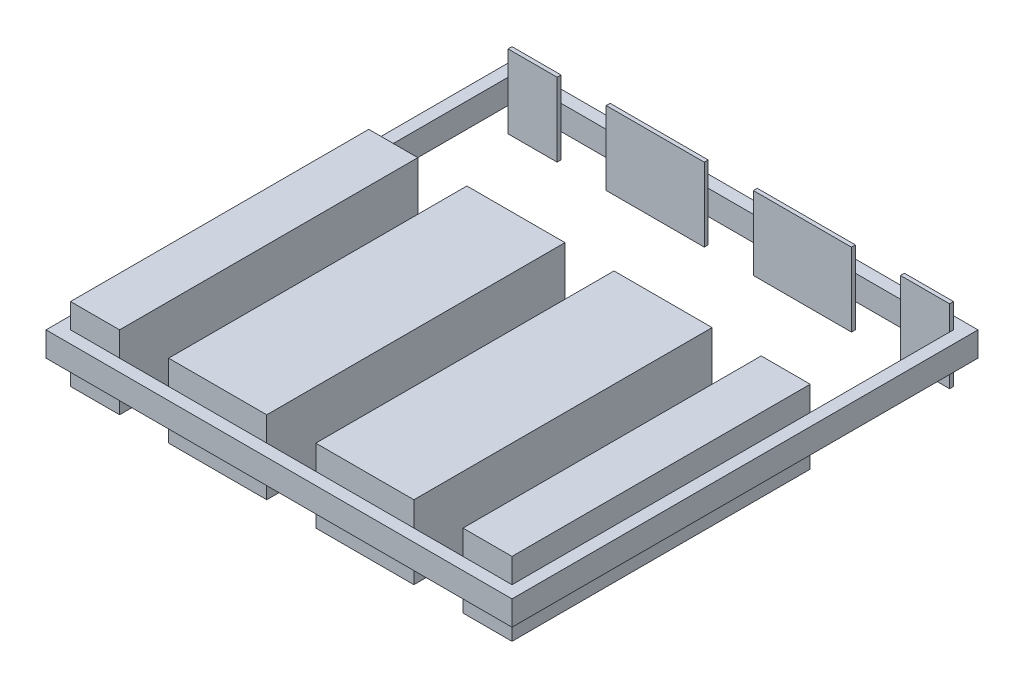
SolidWorks part; units mm, degrees
material "ABS"
ref_plane "Front Plane" through (0, 0, 0) normal (0, 0, 1) x (1, 0, 0)
ref_plane "Top Plane" through (0, 0, 0) normal (0, 1, 0) x (1, 0, 0)
ref_plane "Right Plane" through (0, 0, 0) normal (1, 0, 0) x (0, 0, -1)
sketch "Sketch1" plane through (0, 0, 0) normal (0, 0, 1) x (1, 0, 0)
  line L1 (-90, -15) -> (90, -15)
  line L2 (-90, -15) -> (-90, 15)
  line L3 (-90, 15) -> (90, 15)
  line L4 (90, -15) -> (90, 15)
  line L5 (0, 15) -> (0, -15) construction
  line L6 (-90, 0) -> (90, 0) construction
  point P16 (0, 0)
extrude "Boss-Extrude1" add sketch "Sketch1" along normal mid plane 180
sketch "Sketch2" plane through (0, 0, 0) normal (0, 0, 1) x (1, 0, 0)
  line L0 (-90, -15) -> (90, -15) construction
  line L1 (-70, -15) -> (-50, -15)
  line L2 (-70, -15) -> (-70, 15)
  line L3 (-70, 15) -> (-50, 15)
  line L4 (-50, -15) -> (-50, 15)
  line L5 (-60, 15) -> (-60, -15) construction
  line L6 (-70, 0) -> (-50, 0) construction
  line L7 (90, 15) -> (-90, 15) construction
  line L9 (-10, -15) -> (10, -15)
  line L10 (-10, -15) -> (-10, 15)
  line L11 (-10, 15) -> (10, 15)
  line L12 (10, -15) -> (10, 15)
  line L13 (0, 15) -> (0, -15) construction
  line L14 (-10, 0) -> (10, 0) construction
  line L15 (50, -15) -> (70, -15)
  line L16 (50, -15) -> (50, 15)
  line L17 (50, 15) -> (70, 15)
  line L18 (70, -15) -> (70, 15)
  line L19 (60, 15) -> (60, -15) construction
  line L20 (50, 0) -> (70, 0) construction
  point P20 (-60, 0)
  point P33 (0, 0)
  point P42 (60, 0)
extrude "Cut-Extrude1" cut sketch "Sketch2" against normal mid plane 180
sketch "Sketch3" plane through (0, 0, 0) normal (0, 0, 1) x (1, 0, 0)
  line L1 (-88.4, -13.4) -> (-71.6, -13.4)
  line L2 (-88.4, -13.4) -> (-88.4, 13.4)
  line L3 (-88.4, 13.4) -> (-71.6, 13.4)
  line L4 (-71.6, -13.4) -> (-71.6, 13.4)
  line L5 (-80, 13.4) -> (-80, -13.4) construction
  line L6 (-88.4, 0) -> (-71.6, 0) construction
  line L7 (-48.4, -13.4) -> (-31.6, -13.4)
  line L8 (-48.4, -13.4) -> (-48.4, 13.4)
  line L9 (-48.4, 13.4) -> (-31.6, 13.4)
  line L10 (-31.6, -13.4) -> (-31.6, 13.4)
  line L11 (-40, 13.4) -> (-40, -13.4) construction
  line L12 (-48.4, 0) -> (-31.6, 0) construction
  line L13 (-28.4, -13.4) -> (-11.6, -13.4)
  line L14 (-28.4, -13.4) -> (-28.4, 13.4)
  line L15 (-28.4, 13.4) -> (-11.6, 13.4)
  line L16 (-11.6, -13.4) -> (-11.6, 13.4)
  line L17 (-20, 13.4) -> (-20, -13.4) construction
  line L18 (-28.4, 0) -> (-11.6, 0) construction
  line L19 (11.6, -13.4) -> (28.4, -13.4)
  line L20 (11.6, -13.4) -> (11.6, 13.4)
  line L21 (11.6, 13.4) -> (28.4, 13.4)
  line L22 (28.4, -13.4) -> (28.4, 13.4)
  line L23 (20, 13.4) -> (20, -13.4) construction
  line L24 (11.6, 0) -> (28.4, 0) construction
  line L25 (31.6, -13.4) -> (48.4, -13.4)
  line L26 (31.6, -13.4) -> (31.6, 13.4)
  line L27 (31.6, 13.4) -> (48.4, 13.4)
  line L28 (48.4, -13.4) -> (48.4, 13.4)
  line L29 (40, 13.4) -> (40, -13.4) construction
  line L30 (31.6, 0) -> (48.4, 0) construction
  line L31 (71.6, -13.4) -> (88.4, -13.4)
  line L32 (71.6, -13.4) -> (71.6, 13.4)
  line L33 (71.6, 13.4) -> (88.4, 13.4)
  line L34 (88.4, -13.4) -> (88.4, 13.4)
  line L35 (80, 13.4) -> (80, -13.4) construction
  line L36 (71.6, 0) -> (88.4, 0) construction
  point P16 (-80, 0)
  point P25 (-40, 0)
  point P34 (-20, 0)
  point P43 (20, 0)
  point P52 (40, 0)
  point P61 (80, 0)
extrude "Cut-Extrude2" cut sketch "Sketch3" against normal blind 56.8 from offset 31.6 flip side to cut offset against normal yes
sketch "Sketch4" plane through (0, 0, 0) normal (0, 0, 1) x (1, 0, 0)
  line L1 (-88.4, -13.4) -> (-71.6, -13.4)
  line L2 (-88.4, -13.4) -> (-88.4, 13.4)
  line L3 (-88.4, 13.4) -> (-71.6, 13.4)
  line L4 (-71.6, -13.4) -> (-71.6, 13.4)
  line L5 (-80, 13.4) -> (-80, -13.4) construction
  line L6 (-88.4, 0) -> (-71.6, 0) construction
  line L7 (-48.4, -13.4) -> (-31.6, -13.4)
  line L8 (-48.4, -13.4) -> (-48.4, 13.4)
  line L9 (-48.4, 13.4) -> (-31.6, 13.4)
  line L10 (-31.6, -13.4) -> (-31.6, 13.4)
  line L11 (-40, 13.4) -> (-40, -13.4) construction
  line L12 (-48.4, 0) -> (-31.6, 0) construction
  line L13 (-28.4, -13.4) -> (-11.6, -13.4)
  line L14 (-28.4, -13.4) -> (-28.4, 13.4)
  line L15 (-28.4, 13.4) -> (-11.6, 13.4)
  line L16 (-11.6, -13.4) -> (-11.6, 13.4)
  line L17 (-20, 13.4) -> (-20, -13.4) construction
  line L18 (-28.4, 0) -> (-11.6, 0) construction
  line L19 (11.6, -13.4) -> (28.4, -13.4)
  line L20 (11.6, -13.4) -> (11.6, 13.4)
  line L21 (11.6, 13.4) -> (28.4, 13.4)
  line L22 (28.4, -13.4) -> (28.4, 13.4)
  line L23 (20, 13.4) -> (20, -13.4) construction
  line L24 (11.6, 0) -> (28.4, 0) construction
  line L25 (31.6, -13.4) -> (48.4, -13.4)
  line L26 (31.6, -13.4) -> (31.6, 13.4)
  line L27 (31.6, 13.4) -> (48.4, 13.4)
  line L28 (48.4, -13.4) -> (48.4, 13.4)
  line L29 (40, 13.4) -> (40, -13.4) construction
  line L30 (31.6, 0) -> (48.4, 0) construction
  line L31 (71.6, -13.4) -> (88.4, -13.4)
  line L32 (71.6, -13.4) -> (71.6, 13.4)
  line L33 (71.6, 13.4) -> (88.4, 13.4)
  line L34 (88.4, -13.4) -> (88.4, 13.4)
  line L35 (80, 13.4) -> (80, -13.4) construction
  line L36 (71.6, 0) -> (88.4, 0) construction
  point P16 (-80, 0)
  point P25 (-40, 0)
  point P34 (-20, 0)
  point P43 (20, 0)
  point P52 (40, 0)
  point P61 (80, 0)
extrude "Cut-Extrude3" cut sketch "Sketch4" against normal mid plane 56.8
sketch "Sketch5" plane through (0, 0, 0) normal (0, 0, 1) x (1, 0, 0)
  line L1 (-88.4, -13.4) -> (-71.6, -13.4)
  line L2 (-88.4, -13.4) -> (-88.4, 13.4)
  line L3 (-88.4, 13.4) -> (-71.6, 13.4)
  line L4 (-71.6, -13.4) -> (-71.6, 13.4)
  line L5 (-80, 13.4) -> (-80, -13.4) construction
  line L6 (-88.4, 0) -> (-71.6, 0) construction
  line L7 (-48.4, -13.4) -> (-31.6, -13.4)
  line L8 (-48.4, -13.4) -> (-48.4, 13.4)
  line L9 (-48.4, 13.4) -> (-31.6, 13.4)
  line L10 (-31.6, -13.4) -> (-31.6, 13.4)
  line L11 (-40, 13.4) -> (-40, -13.4) construction
  line L12 (-48.4, 0) -> (-31.6, 0) construction
  line L13 (-28.4, -13.4) -> (-11.6, -13.4)
  line L14 (-28.4, -13.4) -> (-28.4, 13.4)
  line L15 (-28.4, 13.4) -> (-11.6, 13.4)
  line L16 (-11.6, -13.4) -> (-11.6, 13.4)
  line L17 (-20, 13.4) -> (-20, -13.4) construction
  line L18 (-28.4, 0) -> (-11.6, 0) construction
  line L19 (11.6, -13.4) -> (28.4, -13.4)
  line L20 (11.6, -13.4) -> (11.6, 13.4)
  line L21 (11.6, 13.4) -> (28.4, 13.4)
  line L22 (28.4, -13.4) -> (28.4, 13.4)
  line L23 (20, 13.4) -> (20, -13.4) construction
  line L24 (11.6, 0) -> (28.4, 0) construction
  line L25 (31.6, -13.4) -> (48.4, -13.4)
  line L26 (31.6, -13.4) -> (31.6, 13.4)
  line L27 (31.6, 13.4) -> (48.4, 13.4)
  line L28 (48.4, -13.4) -> (48.4, 13.4)
  line L29 (40, 13.4) -> (40, -13.4) construction
  line L30 (31.6, 0) -> (48.4, 0) construction
  line L31 (71.6, -13.4) -> (88.4, -13.4)
  line L32 (71.6, -13.4) -> (71.6, 13.4)
  line L33 (71.6, 13.4) -> (88.4, 13.4)
  line L34 (88.4, -13.4) -> (88.4, 13.4)
  line L35 (80, 13.4) -> (80, -13.4) construction
  line L36 (71.6, 0) -> (88.4, 0) construction
  point P16 (-80, 0)
  point P25 (-40, 0)
  point P34 (-20, 0)
  point P43 (20, 0)
  point P52 (40, 0)
  point P61 (80, 0)
extrude "Cut-Extrude4" cut sketch "Sketch5" against normal blind 56.8 from offset 31.6
sketch "Sketch6" plane through (0, 0, 0) normal (0, 0, 1) x (1, 0, 0)
  line L1 (-76.2, -13.4) -> (-74.6, -13.4)
  line L2 (-76.2, -13.4) -> (-76.2, 10.4)
  line L3 (-76.2, 10.4) -> (-74.6, 10.4)
  line L4 (-74.6, -13.4) -> (-74.6, 10.4)
  line L5 (-75.4, 10.4) -> (-75.4, -13.4) construction
  line L6 (-76.2, -1.5) -> (-74.6, -1.5) construction
  line L7 (-80.8, -10.4) -> (-79.2, -10.4)
  line L8 (-80.8, -10.4) -> (-80.8, 13.4)
  line L9 (-80.8, 13.4) -> (-79.2, 13.4)
  line L10 (-79.2, -10.4) -> (-79.2, 13.4)
  line L11 (-80, 13.4) -> (-80, -10.4) construction
  line L12 (-80.8, 1.5) -> (-79.2, 1.5) construction
  line L13 (-85.4, -13.4) -> (-83.8, -13.4)
  line L14 (-85.4, -13.4) -> (-85.4, 10.4)
  line L15 (-85.4, 10.4) -> (-83.8, 10.4)
  line L16 (-83.8, -13.4) -> (-83.8, 10.4)
  line L17 (-84.6, 10.4) -> (-84.6, -13.4) construction
  line L18 (-85.4, -1.5) -> (-83.8, -1.5) construction
  line L19 (-45.4, -13.4) -> (-43.8, -13.4)
  line L20 (-45.4, -13.4) -> (-45.4, 10.4)
  line L21 (-45.4, 10.4) -> (-43.8, 10.4)
  line L22 (-43.8, -13.4) -> (-43.8, 10.4)
  line L23 (-44.6, 10.4) -> (-44.6, -13.4) construction
  line L24 (-45.4, -1.5) -> (-43.8, -1.5) construction
  line L25 (-40.8, -10.4) -> (-39.2, -10.4)
  line L26 (-40.8, -10.4) -> (-40.8, 13.4)
  line L27 (-40.8, 13.4) -> (-39.2, 13.4)
  line L28 (-39.2, -10.4) -> (-39.2, 13.4)
  line L29 (-40, 13.4) -> (-40, -10.4) construction
  line L30 (-40.8, 1.5) -> (-39.2, 1.5) construction
  line L31 (-36.2, -13.4) -> (-34.6, -13.4)
  line L32 (-36.2, -13.4) -> (-36.2, 10.4)
  line L33 (-36.2, 10.4) -> (-34.6, 10.4)
  line L34 (-34.6, -13.4) -> (-34.6, 10.4)
  line L35 (-35.4, 10.4) -> (-35.4, -13.4) construction
  line L36 (-36.2, -1.5) -> (-34.6, -1.5) construction
  line L37 (-16.2, -13.4) -> (-14.6, -13.4)
  line L38 (-16.2, -13.4) -> (-16.2, 10.4)
  line L39 (-16.2, 10.4) -> (-14.6, 10.4)
  line L40 (-14.6, -13.4) -> (-14.6, 10.4)
  line L41 (-15.4, 10.4) -> (-15.4, -13.4) construction
  line L42 (-16.2, -1.5) -> (-14.6, -1.5) construction
  line L43 (-20.8, -10.4) -> (-19.2, -10.4)
  line L44 (-20.8, -10.4) -> (-20.8, 13.4)
  line L45 (-20.8, 13.4) -> (-19.2, 13.4)
  line L46 (-19.2, -10.4) -> (-19.2, 13.4)
  line L47 (-20, 13.4) -> (-20, -10.4) construction
  line L48 (-20.8, 1.5) -> (-19.2, 1.5) construction
  line L49 (-25.4, -13.4) -> (-23.8, -13.4)
  line L50 (-25.4, -13.4) -> (-25.4, 10.4)
  line L51 (-25.4, 10.4) -> (-23.8, 10.4)
  line L52 (-23.8, -13.4) -> (-23.8, 10.4)
  line L53 (-24.6, 10.4) -> (-24.6, -13.4) construction
  line L54 (-25.4, -1.5) -> (-23.8, -1.5) construction
  line L55 (14.6, -13.4) -> (16.2, -13.4)
  line L56 (14.6, -13.4) -> (14.6, 10.4)
  line L57 (14.6, 10.4) -> (16.2, 10.4)
  line L58 (16.2, -13.4) -> (16.2, 10.4)
  line L59 (15.4, 10.4) -> (15.4, -13.4) construction
  line L60 (14.6, -1.5) -> (16.2, -1.5) construction
  line L61 (19.2, -10.4) -> (20.8, -10.4)
  line L62 (19.2, -10.4) -> (19.2, 13.4)
  line L63 (19.2, 13.4) -> (20.8, 13.4)
  line L64 (20.8, -10.4) -> (20.8, 13.4)
  line L65 (20, 13.4) -> (20, -10.4) construction
  line L66 (19.2, 1.5) -> (20.8, 1.5) construction
  line L67 (23.8, -13.4) -> (25.4, -13.4)
  line L68 (23.8, -13.4) -> (23.8, 10.4)
  line L69 (23.8, 10.4) -> (25.4, 10.4)
  line L70 (25.4, -13.4) -> (25.4, 10.4)
  line L71 (24.6, 10.4) -> (24.6, -13.4) construction
  line L72 (23.8, -1.5) -> (25.4, -1.5) construction
  line L73 (43.8, -13.4) -> (45.4, -13.4)
  line L74 (43.8, -13.4) -> (43.8, 10.4)
  line L75 (43.8, 10.4) -> (45.4, 10.4)
  line L76 (45.4, -13.4) -> (45.4, 10.4)
  line L77 (44.6, 10.4) -> (44.6, -13.4) construction
  line L78 (43.8, -1.5) -> (45.4, -1.5) construction
  line L79 (39.2, -10.4) -> (40.8, -10.4)
  line L80 (39.2, -10.4) -> (39.2, 13.4)
  line L81 (39.2, 13.4) -> (40.8, 13.4)
  line L82 (40.8, -10.4) -> (40.8, 13.4)
  line L83 (40, 13.4) -> (40, -10.4) construction
  line L84 (39.2, 1.5) -> (40.8, 1.5) construction
  line L85 (34.6, -13.4) -> (36.2, -13.4)
  line L86 (34.6, -13.4) -> (34.6, 10.4)
  line L87 (34.6, 10.4) -> (36.2, 10.4)
  line L88 (36.2, -13.4) -> (36.2, 10.4)
  line L89 (35.4, 10.4) -> (35.4, -13.4) construction
  line L90 (34.6, -1.5) -> (36.2, -1.5) construction
  line L91 (74.6, -13.4) -> (76.2, -13.4)
  line L92 (74.6, -13.4) -> (74.6, 10.4)
  line L93 (74.6, 10.4) -> (76.2, 10.4)
  line L94 (76.2, -13.4) -> (76.2, 10.4)
  line L95 (75.4, 10.4) -> (75.4, -13.4) construction
  line L96 (74.6, -1.5) -> (76.2, -1.5) construction
  line L97 (79.2, -10.4) -> (80.8, -10.4)
  line L98 (79.2, -10.4) -> (79.2, 13.4)
  line L99 (79.2, 13.4) -> (80.8, 13.4)
  line L100 (80.8, -10.4) -> (80.8, 13.4)
  line L101 (80, 13.4) -> (80, -10.4) construction
  line L102 (79.2, 1.5) -> (80.8, 1.5) construction
  line L103 (83.8, -13.4) -> (85.4, -13.4)
  line L104 (83.8, -13.4) -> (83.8, 10.4)
  line L105 (83.8, 10.4) -> (85.4, 10.4)
  line L106 (85.4, -13.4) -> (85.4, 10.4)
  line L107 (84.6, 10.4) -> (84.6, -13.4) construction
  line L108 (83.8, -1.5) -> (85.4, -1.5) construction
  point P16 (-75.4, -1.5)
  point P25 (-80, 1.5)
  point P34 (-84.6, -1.5)
  point P43 (-44.6, -1.5)
  point P52 (-40, 1.5)
  point P61 (-35.4, -1.5)
  point P70 (-15.4, -1.5)
  point P79 (-20, 1.5)
  point P88 (-24.6, -1.5)
  point P97 (15.4, -1.5)
  point P106 (20, 1.5)
  point P115 (24.6, -1.5)
  point P124 (44.6, -1.5)
  point P133 (40, 1.5)
  point P142 (35.4, -1.5)
  point P151 (75.4, -1.5)
  point P160 (80, 1.5)
  point P169 (84.6, -1.5)
extrude "Boss-Extrude2" add sketch "Sketch6" along normal blind 56.8 from offset 31.6 flip side to cut offset against normal yes
sketch "Sketch7" plane through (0, 0, 0) normal (0, 0, 1) x (1, 0, 0)
  line L1 (-76.2, -13.4) -> (-74.6, -13.4)
  line L2 (-76.2, -13.4) -> (-76.2, 10.4)
  line L3 (-76.2, 10.4) -> (-74.6, 10.4)
  line L4 (-74.6, -13.4) -> (-74.6, 10.4)
  line L5 (-75.4, 10.4) -> (-75.4, -13.4) construction
  line L6 (-76.2, -1.5) -> (-74.6, -1.5) construction
  line L7 (-80.8, -10.4) -> (-79.2, -10.4)
  line L8 (-80.8, -10.4) -> (-80.8, 13.4)
  line L9 (-80.8, 13.4) -> (-79.2, 13.4)
  line L10 (-79.2, -10.4) -> (-79.2, 13.4)
  line L11 (-80, 13.4) -> (-80, -10.4) construction
  line L12 (-80.8, 1.5) -> (-79.2, 1.5) construction
  line L13 (-85.4, -13.4) -> (-83.8, -13.4)
  line L14 (-85.4, -13.4) -> (-85.4, 10.4)
  line L15 (-85.4, 10.4) -> (-83.8, 10.4)
  line L16 (-83.8, -13.4) -> (-83.8, 10.4)
  line L17 (-84.6, 10.4) -> (-84.6, -13.4) construction
  line L18 (-85.4, -1.5) -> (-83.8, -1.5) construction
  line L19 (-45.4, -13.4) -> (-43.8, -13.4)
  line L20 (-45.4, -13.4) -> (-45.4, 10.4)
  line L21 (-45.4, 10.4) -> (-43.8, 10.4)
  line L22 (-43.8, -13.4) -> (-43.8, 10.4)
  line L23 (-44.6, 10.4) -> (-44.6, -13.4) construction
  line L24 (-45.4, -1.5) -> (-43.8, -1.5) construction
  line L25 (-40.8, -10.4) -> (-39.2, -10.4)
  line L26 (-40.8, -10.4) -> (-40.8, 13.4)
  line L27 (-40.8, 13.4) -> (-39.2, 13.4)
  line L28 (-39.2, -10.4) -> (-39.2, 13.4)
  line L29 (-40, 13.4) -> (-40, -10.4) construction
  line L30 (-40.8, 1.5) -> (-39.2, 1.5) construction
  line L31 (-36.2, -13.4) -> (-34.6, -13.4)
  line L32 (-36.2, -13.4) -> (-36.2, 10.4)
  line L33 (-36.2, 10.4) -> (-34.6, 10.4)
  line L34 (-34.6, -13.4) -> (-34.6, 10.4)
  line L35 (-35.4, 10.4) -> (-35.4, -13.4) construction
  line L36 (-36.2, -1.5) -> (-34.6, -1.5) construction
  line L37 (-16.2, -13.4) -> (-14.6, -13.4)
  line L38 (-16.2, -13.4) -> (-16.2, 10.4)
  line L39 (-16.2, 10.4) -> (-14.6, 10.4)
  line L40 (-14.6, -13.4) -> (-14.6, 10.4)
  line L41 (-15.4, 10.4) -> (-15.4, -13.4) construction
  line L42 (-16.2, -1.5) -> (-14.6, -1.5) construction
  line L43 (-20.8, -10.4) -> (-19.2, -10.4)
  line L44 (-20.8, -10.4) -> (-20.8, 13.4)
  line L45 (-20.8, 13.4) -> (-19.2, 13.4)
  line L46 (-19.2, -10.4) -> (-19.2, 13.4)
  line L47 (-20, 13.4) -> (-20, -10.4) construction
  line L48 (-20.8, 1.5) -> (-19.2, 1.5) construction
  line L49 (-25.4, -13.4) -> (-23.8, -13.4)
  line L50 (-25.4, -13.4) -> (-25.4, 10.4)
  line L51 (-25.4, 10.4) -> (-23.8, 10.4)
  line L52 (-23.8, -13.4) -> (-23.8, 10.4)
  line L53 (-24.6, 10.4) -> (-24.6, -13.4) construction
  line L54 (-25.4, -1.5) -> (-23.8, -1.5) construction
  line L55 (14.6, -13.4) -> (16.2, -13.4)
  line L56 (14.6, -13.4) -> (14.6, 10.4)
  line L57 (14.6, 10.4) -> (16.2, 10.4)
  line L58 (16.2, -13.4) -> (16.2, 10.4)
  line L59 (15.4, 10.4) -> (15.4, -13.4) construction
  line L60 (14.6, -1.5) -> (16.2, -1.5) construction
  line L61 (19.2, -10.4) -> (20.8, -10.4)
  line L62 (19.2, -10.4) -> (19.2, 13.4)
  line L63 (19.2, 13.4) -> (20.8, 13.4)
  line L64 (20.8, -10.4) -> (20.8, 13.4)
  line L65 (20, 13.4) -> (20, -10.4) construction
  line L66 (19.2, 1.5) -> (20.8, 1.5) construction
  line L67 (23.8, -13.4) -> (25.4, -13.4)
  line L68 (23.8, -13.4) -> (23.8, 10.4)
  line L69 (23.8, 10.4) -> (25.4, 10.4)
  line L70 (25.4, -13.4) -> (25.4, 10.4)
  line L71 (24.6, 10.4) -> (24.6, -13.4) construction
  line L72 (23.8, -1.5) -> (25.4, -1.5) construction
  line L73 (43.8, -13.4) -> (45.4, -13.4)
  line L74 (43.8, -13.4) -> (43.8, 10.4)
  line L75 (43.8, 10.4) -> (45.4, 10.4)
  line L76 (45.4, -13.4) -> (45.4, 10.4)
  line L77 (44.6, 10.4) -> (44.6, -13.4) construction
  line L78 (43.8, -1.5) -> (45.4, -1.5) construction
  line L79 (39.2, -10.4) -> (40.8, -10.4)
  line L80 (39.2, -10.4) -> (39.2, 13.4)
  line L81 (39.2, 13.4) -> (40.8, 13.4)
  line L82 (40.8, -10.4) -> (40.8, 13.4)
  line L83 (40, 13.4) -> (40, -10.4) construction
  line L84 (39.2, 1.5) -> (40.8, 1.5) construction
  line L85 (34.6, -13.4) -> (36.2, -13.4)
  line L86 (34.6, -13.4) -> (34.6, 10.4)
  line L87 (34.6, 10.4) -> (36.2, 10.4)
  line L88 (36.2, -13.4) -> (36.2, 10.4)
  line L89 (35.4, 10.4) -> (35.4, -13.4) construction
  line L90 (34.6, -1.5) -> (36.2, -1.5) construction
  line L91 (74.6, -13.4) -> (76.2, -13.4)
  line L92 (74.6, -13.4) -> (74.6, 10.4)
  line L93 (74.6, 10.4) -> (76.2, 10.4)
  line L94 (76.2, -13.4) -> (76.2, 10.4)
  line L95 (75.4, 10.4) -> (75.4, -13.4) construction
  line L96 (74.6, -1.5) -> (76.2, -1.5) construction
  line L97 (79.2, -10.4) -> (80.8, -10.4)
  line L98 (79.2, -10.4) -> (79.2, 13.4)
  line L99 (79.2, 13.4) -> (80.8, 13.4)
  line L100 (80.8, -10.4) -> (80.8, 13.4)
  line L101 (80, 13.4) -> (80, -10.4) construction
  line L102 (79.2, 1.5) -> (80.8, 1.5) construction
  line L103 (83.8, -13.4) -> (85.4, -13.4)
  line L104 (83.8, -13.4) -> (83.8, 10.4)
  line L105 (83.8, 10.4) -> (85.4, 10.4)
  line L106 (85.4, -13.4) -> (85.4, 10.4)
  line L107 (84.6, 10.4) -> (84.6, -13.4) construction
  line L108 (83.8, -1.5) -> (85.4, -1.5) construction
  point P16 (-75.4, -1.5)
  point P25 (-80, 1.5)
  point P34 (-84.6, -1.5)
  point P43 (-44.6, -1.5)
  point P52 (-40, 1.5)
  point P61 (-35.4, -1.5)
  point P70 (-15.4, -1.5)
  point P79 (-20, 1.5)
  point P88 (-24.6, -1.5)
  point P97 (15.4, -1.5)
  point P106 (20, 1.5)
  point P115 (24.6, -1.5)
  point P124 (44.6, -1.5)
  point P133 (40, 1.5)
  point P142 (35.4, -1.5)
  point P151 (75.4, -1.5)
  point P160 (80, 1.5)
  point P169 (84.6, -1.5)
extrude "Boss-Extrude3" add sketch "Sketch7" along normal mid plane 56.8
sketch "Sketch8" plane through (0, 0, 0) normal (0, 0, 1) x (1, 0, 0)
  line L1 (-76.2, -13.4) -> (-74.6, -13.4)
  line L2 (-76.2, -13.4) -> (-76.2, 10.4)
  line L3 (-76.2, 10.4) -> (-74.6, 10.4)
  line L4 (-74.6, -13.4) -> (-74.6, 10.4)
  line L5 (-75.4, 10.4) -> (-75.4, -13.4) construction
  line L6 (-76.2, -1.5) -> (-74.6, -1.5) construction
  line L7 (-80.8, -10.4) -> (-79.2, -10.4)
  line L8 (-80.8, -10.4) -> (-80.8, 13.4)
  line L9 (-80.8, 13.4) -> (-79.2, 13.4)
  line L10 (-79.2, -10.4) -> (-79.2, 13.4)
  line L11 (-80, 13.4) -> (-80, -10.4) construction
  line L12 (-80.8, 1.5) -> (-79.2, 1.5) construction
  line L13 (-85.4, -13.4) -> (-83.8, -13.4)
  line L14 (-85.4, -13.4) -> (-85.4, 10.4)
  line L15 (-85.4, 10.4) -> (-83.8, 10.4)
  line L16 (-83.8, -13.4) -> (-83.8, 10.4)
  line L17 (-84.6, 10.4) -> (-84.6, -13.4) construction
  line L18 (-85.4, -1.5) -> (-83.8, -1.5) construction
  line L19 (-45.4, -13.4) -> (-43.8, -13.4)
  line L20 (-45.4, -13.4) -> (-45.4, 10.4)
  line L21 (-45.4, 10.4) -> (-43.8, 10.4)
  line L22 (-43.8, -13.4) -> (-43.8, 10.4)
  line L23 (-44.6, 10.4) -> (-44.6, -13.4) construction
  line L24 (-45.4, -1.5) -> (-43.8, -1.5) construction
  line L25 (-40.8, -10.4) -> (-39.2, -10.4)
  line L26 (-40.8, -10.4) -> (-40.8, 13.4)
  line L27 (-40.8, 13.4) -> (-39.2, 13.4)
  line L28 (-39.2, -10.4) -> (-39.2, 13.4)
  line L29 (-40, 13.4) -> (-40, -10.4) construction
  line L30 (-40.8, 1.5) -> (-39.2, 1.5) construction
  line L31 (-36.2, -13.4) -> (-34.6, -13.4)
  line L32 (-36.2, -13.4) -> (-36.2, 10.4)
  line L33 (-36.2, 10.4) -> (-34.6, 10.4)
  line L34 (-34.6, -13.4) -> (-34.6, 10.4)
  line L35 (-35.4, 10.4) -> (-35.4, -13.4) construction
  line L36 (-36.2, -1.5) -> (-34.6, -1.5) construction
  line L37 (-16.2, -13.4) -> (-14.6, -13.4)
  line L38 (-16.2, -13.4) -> (-16.2, 10.4)
  line L39 (-16.2, 10.4) -> (-14.6, 10.4)
  line L40 (-14.6, -13.4) -> (-14.6, 10.4)
  line L41 (-15.4, 10.4) -> (-15.4, -13.4) construction
  line L42 (-16.2, -1.5) -> (-14.6, -1.5) construction
  line L43 (-20.8, -10.4) -> (-19.2, -10.4)
  line L44 (-20.8, -10.4) -> (-20.8, 13.4)
  line L45 (-20.8, 13.4) -> (-19.2, 13.4)
  line L46 (-19.2, -10.4) -> (-19.2, 13.4)
  line L47 (-20, 13.4) -> (-20, -10.4) construction
  line L48 (-20.8, 1.5) -> (-19.2, 1.5) construction
  line L49 (-25.4, -13.4) -> (-23.8, -13.4)
  line L50 (-25.4, -13.4) -> (-25.4, 10.4)
  line L51 (-25.4, 10.4) -> (-23.8, 10.4)
  line L52 (-23.8, -13.4) -> (-23.8, 10.4)
  line L53 (-24.6, 10.4) -> (-24.6, -13.4) construction
  line L54 (-25.4, -1.5) -> (-23.8, -1.5) construction
  line L55 (14.6, -13.4) -> (16.2, -13.4)
  line L56 (14.6, -13.4) -> (14.6, 10.4)
  line L57 (14.6, 10.4) -> (16.2, 10.4)
  line L58 (16.2, -13.4) -> (16.2, 10.4)
  line L59 (15.4, 10.4) -> (15.4, -13.4) construction
  line L60 (14.6, -1.5) -> (16.2, -1.5) construction
  line L61 (19.2, -10.4) -> (20.8, -10.4)
  line L62 (19.2, -10.4) -> (19.2, 13.4)
  line L63 (19.2, 13.4) -> (20.8, 13.4)
  line L64 (20.8, -10.4) -> (20.8, 13.4)
  line L65 (20, 13.4) -> (20, -10.4) construction
  line L66 (19.2, 1.5) -> (20.8, 1.5) construction
  line L67 (23.8, -13.4) -> (25.4, -13.4)
  line L68 (23.8, -13.4) -> (23.8, 10.4)
  line L69 (23.8, 10.4) -> (25.4, 10.4)
  line L70 (25.4, -13.4) -> (25.4, 10.4)
  line L71 (24.6, 10.4) -> (24.6, -13.4) construction
  line L72 (23.8, -1.5) -> (25.4, -1.5) construction
  line L73 (43.8, -13.4) -> (45.4, -13.4)
  line L74 (43.8, -13.4) -> (43.8, 10.4)
  line L75 (43.8, 10.4) -> (45.4, 10.4)
  line L76 (45.4, -13.4) -> (45.4, 10.4)
  line L77 (44.6, 10.4) -> (44.6, -13.4) construction
  line L78 (43.8, -1.5) -> (45.4, -1.5) construction
  line L79 (39.2, -10.4) -> (40.8, -10.4)
  line L80 (39.2, -10.4) -> (39.2, 13.4)
  line L81 (39.2, 13.4) -> (40.8, 13.4)
  line L82 (40.8, -10.4) -> (40.8, 13.4)
  line L83 (40, 13.4) -> (40, -10.4) construction
  line L84 (39.2, 1.5) -> (40.8, 1.5) construction
  line L85 (34.6, -13.4) -> (36.2, -13.4)
  line L86 (34.6, -13.4) -> (34.6, 10.4)
  line L87 (34.6, 10.4) -> (36.2, 10.4)
  line L88 (36.2, -13.4) -> (36.2, 10.4)
  line L89 (35.4, 10.4) -> (35.4, -13.4) construction
  line L90 (34.6, -1.5) -> (36.2, -1.5) construction
  line L91 (74.6, -13.4) -> (76.2, -13.4)
  line L92 (74.6, -13.4) -> (74.6, 10.4)
  line L93 (74.6, 10.4) -> (76.2, 10.4)
  line L94 (76.2, -13.4) -> (76.2, 10.4)
  line L95 (75.4, 10.4) -> (75.4, -13.4) construction
  line L96 (74.6, -1.5) -> (76.2, -1.5) construction
  line L97 (79.2, -10.4) -> (80.8, -10.4)
  line L98 (79.2, -10.4) -> (79.2, 13.4)
  line L99 (79.2, 13.4) -> (80.8, 13.4)
  line L100 (80.8, -10.4) -> (80.8, 13.4)
  line L101 (80, 13.4) -> (80, -10.4) construction
  line L102 (79.2, 1.5) -> (80.8, 1.5) construction
  line L103 (83.8, -13.4) -> (85.4, -13.4)
  line L104 (83.8, -13.4) -> (83.8, 10.4)
  line L105 (83.8, 10.4) -> (85.4, 10.4)
  line L106 (85.4, -13.4) -> (85.4, 10.4)
  line L107 (84.6, 10.4) -> (84.6, -13.4) construction
  line L108 (83.8, -1.5) -> (85.4, -1.5) construction
  point P16 (-75.4, -1.5)
  point P25 (-80, 1.5)
  point P34 (-84.6, -1.5)
  point P43 (-44.6, -1.5)
  point P52 (-40, 1.5)
  point P61 (-35.4, -1.5)
  point P70 (-15.4, -1.5)
  point P79 (-20, 1.5)
  point P88 (-24.6, -1.5)
  point P97 (15.4, -1.5)
  point P106 (20, 1.5)
  point P115 (24.6, -1.5)
  point P124 (44.6, -1.5)
  point P133 (40, 1.5)
  point P142 (35.4, -1.5)
  point P151 (75.4, -1.5)
  point P160 (80, 1.5)
  point P169 (84.6, -1.5)
extrude "Boss-Extrude4" add sketch "Sketch8" along normal blind 56.8 from offset 31.6
sketch "Sketch9" plane through (0, 0, 0) normal (0, 0, 1) x (1, 0, 0)
  line L0 (-70, 15) -> (-70, -15) construction
  line L1 (-71.6, -13.4) -> (-70, -13.4)
  line L2 (-71.6, -13.4) -> (-71.6, -10.4)
  line L3 (-71.6, -10.4) -> (-70, -10.4)
  line L4 (-70, -13.4) -> (-70, -10.4)
  line L5 (-70.8, -10.4) -> (-70.8, -13.4) construction
  line L6 (-71.6, -11.9) -> (-70, -11.9) construction
  line L7 (-50, -15) -> (-50, 15) construction
  line L8 (-50, -13.4) -> (-48.4, -13.4)
  line L9 (-50, -13.4) -> (-50, -10.4)
  line L10 (-50, -10.4) -> (-48.4, -10.4)
  line L11 (-48.4, -13.4) -> (-48.4, -10.4)
  line L12 (-49.2, -10.4) -> (-49.2, -13.4) construction
  line L13 (-50, -11.9) -> (-48.4, -11.9) construction
  line L14 (-10, 15) -> (-10, -15) construction
  line L15 (-11.6, -13.4) -> (-10, -13.4)
  line L16 (-11.6, -13.4) -> (-11.6, -10.4)
  line L17 (-11.6, -10.4) -> (-10, -10.4)
  line L18 (-10, -13.4) -> (-10, -10.4)
  line L19 (-10.8, -10.4) -> (-10.8, -13.4) construction
  line L20 (-11.6, -11.9) -> (-10, -11.9) construction
  line L21 (10, -15) -> (10, 15) construction
  line L22 (10, -13.4) -> (11.6, -13.4)
  line L23 (10, -13.4) -> (10, -10.4)
  line L24 (10, -10.4) -> (11.6, -10.4)
  line L25 (11.6, -13.4) -> (11.6, -10.4)
  line L26 (10.8, -10.4) -> (10.8, -13.4) construction
  line L27 (10, -11.9) -> (11.6, -11.9) construction
  line L28 (50, 15) -> (50, -15) construction
  line L29 (48.4, -13.4) -> (50, -13.4)
  line L30 (48.4, -13.4) -> (48.4, -10.4)
  line L31 (48.4, -10.4) -> (50, -10.4)
  line L32 (50, -13.4) -> (50, -10.4)
  line L33 (49.2, -10.4) -> (49.2, -13.4) construction
  line L34 (48.4, -11.9) -> (50, -11.9) construction
  line L35 (70, -15) -> (70, 15) construction
  line L36 (70, -13.4) -> (71.6, -13.4)
  line L37 (70, -13.4) -> (70, -10.4)
  line L38 (70, -10.4) -> (71.6, -10.4)
  line L39 (71.6, -13.4) -> (71.6, -10.4)
  line L40 (70.8, -10.4) -> (70.8, -13.4) construction
  line L41 (70, -11.9) -> (71.6, -11.9) construction
  point P20 (-70.8, -11.9)
  point P27 (-49.2, -11.9)
  point P42 (-10.8, -11.9)
  point P49 (10.8, -11.9)
  point P64 (49.2, -11.9)
  point P71 (70.8, -11.9)
extrude "Cut-Extrude5" cut sketch "Sketch9" against normal blind 56.8 from offset 31.6 flip side to cut offset against normal yes
sketch "Sketch10" plane through (0, 0, 0) normal (0, 0, 1) x (1, 0, 0)
  line L0 (-70, 15) -> (-70, -15) construction
  line L1 (-71.6, -13.4) -> (-70, -13.4)
  line L2 (-71.6, -13.4) -> (-71.6, -10.4)
  line L3 (-71.6, -10.4) -> (-70, -10.4)
  line L4 (-70, -13.4) -> (-70, -10.4)
  line L5 (-70.8, -10.4) -> (-70.8, -13.4) construction
  line L6 (-71.6, -11.9) -> (-70, -11.9) construction
  line L7 (-50, -15) -> (-50, 15) construction
  line L8 (-50, -13.4) -> (-48.4, -13.4)
  line L9 (-50, -13.4) -> (-50, -10.4)
  line L10 (-50, -10.4) -> (-48.4, -10.4)
  line L11 (-48.4, -13.4) -> (-48.4, -10.4)
  line L12 (-49.2, -10.4) -> (-49.2, -13.4) construction
  line L13 (-50, -11.9) -> (-48.4, -11.9) construction
  line L14 (-10, 15) -> (-10, -15) construction
  line L15 (-11.6, -13.4) -> (-10, -13.4)
  line L16 (-11.6, -13.4) -> (-11.6, -10.4)
  line L17 (-11.6, -10.4) -> (-10, -10.4)
  line L18 (-10, -13.4) -> (-10, -10.4)
  line L19 (-10.8, -10.4) -> (-10.8, -13.4) construction
  line L20 (-11.6, -11.9) -> (-10, -11.9) construction
  line L21 (10, -15) -> (10, 15) construction
  line L22 (10, -13.4) -> (11.6, -13.4)
  line L23 (10, -13.4) -> (10, -10.4)
  line L24 (10, -10.4) -> (11.6, -10.4)
  line L25 (11.6, -13.4) -> (11.6, -10.4)
  line L26 (10.8, -10.4) -> (10.8, -13.4) construction
  line L27 (10, -11.9) -> (11.6, -11.9) construction
  line L28 (50, 15) -> (50, -15) construction
  line L29 (48.4, -13.4) -> (50, -13.4)
  line L30 (48.4, -13.4) -> (48.4, -10.4)
  line L31 (48.4, -10.4) -> (50, -10.4)
  line L32 (50, -13.4) -> (50, -10.4)
  line L33 (49.2, -10.4) -> (49.2, -13.4) construction
  line L34 (48.4, -11.9) -> (50, -11.9) construction
  line L35 (70, -15) -> (70, 15) construction
  line L36 (70, -13.4) -> (71.6, -13.4)
  line L37 (70, -13.4) -> (70, -10.4)
  line L38 (70, -10.4) -> (71.6, -10.4)
  line L39 (71.6, -13.4) -> (71.6, -10.4)
  line L40 (70.8, -10.4) -> (70.8, -13.4) construction
  line L41 (70, -11.9) -> (71.6, -11.9) construction
  point P20 (-70.8, -11.9)
  point P27 (-49.2, -11.9)
  point P42 (-10.8, -11.9)
  point P49 (10.8, -11.9)
  point P64 (49.2, -11.9)
  point P71 (70.8, -11.9)
extrude "Cut-Extrude6" cut sketch "Sketch10" against normal mid plane 56.8
sketch "Sketch11" plane through (0, 0, 0) normal (0, 0, 1) x (1, 0, 0)
  line L0 (-70, 15) -> (-70, -15) construction
  line L1 (-71.6, -13.4) -> (-70, -13.4)
  line L2 (-71.6, -13.4) -> (-71.6, -10.4)
  line L3 (-71.6, -10.4) -> (-70, -10.4)
  line L4 (-70, -13.4) -> (-70, -10.4)
  line L5 (-70.8, -10.4) -> (-70.8, -13.4) construction
  line L6 (-71.6, -11.9) -> (-70, -11.9) construction
  line L7 (-10, 15) -> (-10, -15) construction
  line L8 (-50, -13.4) -> (-48.4, -13.4)
  line L9 (-50, -13.4) -> (-50, -10.4)
  line L10 (-50, -10.4) -> (-48.4, -10.4)
  line L11 (-48.4, -13.4) -> (-48.4, -10.4)
  line L12 (-49.2, -10.4) -> (-49.2, -13.4) construction
  line L13 (-50, -11.9) -> (-48.4, -11.9) construction
  line L14 (-11.6, -13.4) -> (-10, -13.4)
  line L15 (-11.6, -13.4) -> (-11.6, -10.4)
  line L16 (-11.6, -10.4) -> (-10, -10.4)
  line L17 (-10, -13.4) -> (-10, -10.4)
  line L18 (-10.8, -10.4) -> (-10.8, -13.4) construction
  line L19 (-11.6, -11.9) -> (-10, -11.9) construction
  line L20 (50, 15) -> (50, -15) construction
  line L21 (10, -13.4) -> (11.6, -13.4)
  line L22 (10, -13.4) -> (10, -10.4)
  line L23 (10, -10.4) -> (11.6, -10.4)
  line L24 (11.6, -13.4) -> (11.6, -10.4)
  line L25 (10.8, -10.4) -> (10.8, -13.4) construction
  line L26 (10, -11.9) -> (11.6, -11.9) construction
  line L27 (48.4, -13.4) -> (50, -13.4)
  line L28 (48.4, -13.4) -> (48.4, -10.4)
  line L29 (48.4, -10.4) -> (50, -10.4)
  line L30 (50, -13.4) -> (50, -10.4)
  line L31 (49.2, -10.4) -> (49.2, -13.4) construction
  line L32 (48.4, -11.9) -> (50, -11.9) construction
  line L34 (70, -13.4) -> (71.6, -13.4)
  line L35 (70, -13.4) -> (70, -10.4)
  line L36 (70, -10.4) -> (71.6, -10.4)
  line L37 (71.6, -13.4) -> (71.6, -10.4)
  line L38 (70.8, -10.4) -> (70.8, -13.4) construction
  line L39 (70, -11.9) -> (71.6, -11.9) construction
  point P20 (-70.8, -11.9)
  point P27 (-49.2, -11.9)
  point P41 (-10.8, -11.9)
  point P48 (10.8, -11.9)
  point P62 (49.2, -11.9)
  point P69 (70.8, -11.9)
extrude "Cut-Extrude7" cut sketch "Sketch11" against normal blind 56.8 from offset 31.6
sketch "Sketch12" plane through (0, 0, 0) normal (0, 1, 0) x (1, 0, 0)
  line L1 (-95, -95) -> (95, -95)
  line L2 (-95, -95) -> (-95, 95)
  line L3 (-95, 95) -> (95, 95)
  line L4 (95, -95) -> (95, 95)
  line L5 (0, 95) -> (0, -95) construction
  line L6 (-95, 0) -> (95, 0) construction
  line L7 (-90, -90) -> (90, -90)
  line L8 (-90, -90) -> (-90, 90)
  line L9 (-90, 90) -> (90, 90)
  line L10 (90, -90) -> (90, 90)
  line L11 (0, 90) -> (0, -90) construction
  line L12 (-90, 0) -> (90, 0) construction
  point P16 (0, 0)
  point P29 (0, 0)
extrude "Boss-Extrude5" add sketch "Sketch12" along normal mid plane 10
